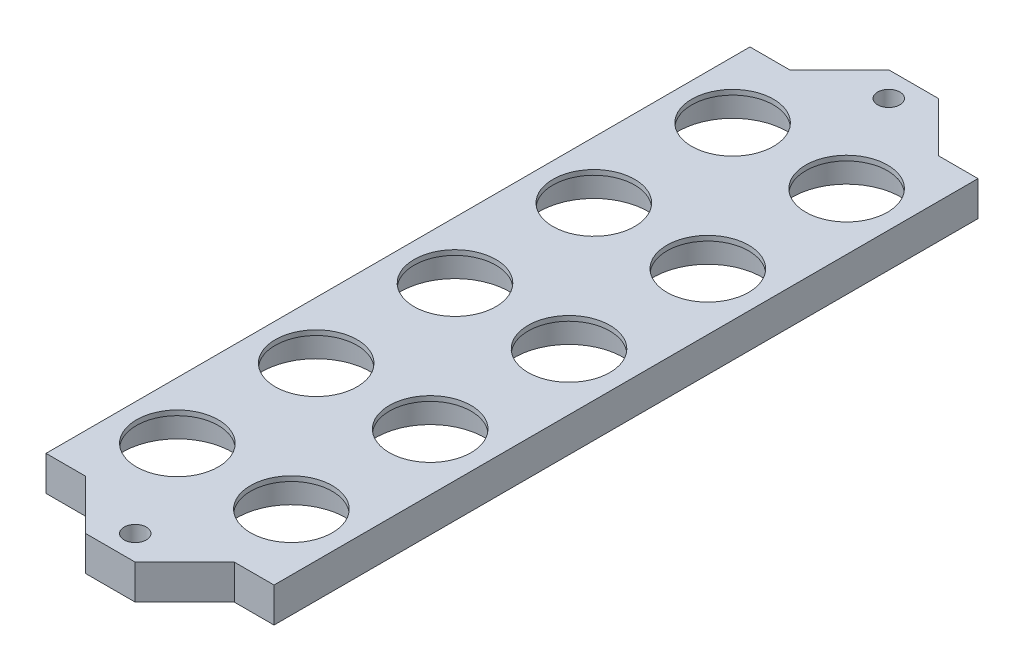
SolidWorks part; units mm, degrees
ref_plane "Front Plane" through (0, 0, 0) normal (0, 0, 1) x (1, 0, 0)
ref_plane "Top Plane" through (0, 0, 0) normal (0, 1, 0) x (1, 0, 0)
ref_plane "Right Plane" through (0, 0, 0) normal (1, 0, 0) x (0, 0, -1)
sketch "Szkic1" plane through (0, 0, 0) normal (0, 1, 0) x (1, 0, 0)
  line L0 (6.5, 25) -> (-3.5, 15)
  line L1 (-11.5, 15) -> (34.5, 15)
  line L2 (-11.5, 15) -> (-11.5, -127)
  line L3 (-11.5, -127) -> (34.5, -127)
  line L4 (34.5, 15) -> (34.5, -127)
  line L5 (6.5, 15) -> (16.5, 15)
  line L6 (6.5, 15) -> (6.5, 25)
  line L7 (6.5, 25) -> (16.5, 25)
  line L8 (16.5, 15) -> (16.5, 25)
  line L9 (16.5, 25) -> (26.5, 15)
  line L12 (-11.5, -56) -> (-33.554, -56) construction
  line L13 (16.5, -137) -> (26.5, -127)
  line L14 (16.5, -127) -> (16.5, -137)
  line L15 (6.5, -127) -> (6.5, -137)
  line L16 (6.5, -137) -> (16.5, -137)
  line L17 (6.5, -137) -> (-3.5, -127)
  line L18 (-11.5, -155) -> (34.5, -155) [skipped]
  line L19 (-11.5, -183) -> (34.5, -183) [skipped]
  circle A0 centre (0, 0) radius 8.25
  circle A1 centre (0, 0) radius 10.6
  circle A2 centre (0, 0) radius 10.1
  circle A3 centre (0, 0) radius 11
  circle A5 centre (23, 0) radius 8.25
  circle A6 centre (23, 0) radius 10.6
  circle A7 centre (23, 0) radius 10.1
  circle A8 centre (23, 0) radius 11
  circle A10 centre (23, -28) radius 8.25
  circle A11 centre (23, -28) radius 10.6
  circle A12 centre (23, -28) radius 10.1
  circle A13 centre (23, -28) radius 11
  circle A15 centre (0, -28) radius 8.25
  circle A16 centre (0, -28) radius 10.6
  circle A17 centre (0, -28) radius 10.1
  circle A18 centre (0, -28) radius 11
  circle A20 centre (0, -56) radius 11
  circle A21 centre (0, -56) radius 10.6
  circle A22 centre (0, -56) radius 10.1
  circle A23 centre (0, -56) radius 8.25
  circle A24 centre (23, -56) radius 8.25
  circle A25 centre (23, -56) radius 10.1
  circle A26 centre (23, -56) radius 10.6
  circle A27 centre (23, -56) radius 11
  circle A28 centre (0, -84) radius 11
  circle A29 centre (0, -84) radius 10.6
  circle A30 centre (0, -84) radius 10.1
  circle A31 centre (0, -84) radius 8.25
  circle A32 centre (23, -84) radius 8.25
  circle A33 centre (23, -84) radius 10.1
  circle A34 centre (23, -84) radius 10.6
  circle A35 centre (23, -84) radius 11
  circle A36 centre (0, -112) radius 11
  circle A37 centre (0, -112) radius 10.6
  circle A38 centre (0, -112) radius 10.1
  circle A39 centre (0, -112) radius 8.25
  circle A40 centre (23, -112) radius 8.25
  circle A41 centre (23, -112) radius 10.1
  circle A42 centre (23, -112) radius 10.6
  circle A43 centre (23, -112) radius 11
  dimension "D1" = 16.5
  dimension "D2" = 20.2
  dimension "D3" = 21.2
  dimension "D4" = 0.4
  dimension "D5" = 23
  dimension "D8" = 11.5
  dimension "D10" = 2
  dimension "D9" = 11.5
  dimension "D11" = 15
  dimension "D12" = 10
  dimension "D13" = 18
  dimension "D14" = 10
  dimension "D15" = 3
  dimension "D16" = 15
  dimension "D17" = 45
  dimension "D18" = 45
  dimension "D6" = 2
  dimension "D7" = 2
extrude "Dodanie-wyciągnięcie1" add sketch "Szkic1" along normal blind 1 contours L4 L1 L2 | L4 L2 | L2 L3 L4 | A18 | A18 A16 | A16 A17 | A17 A15 | A12 A10 | A11 A12 | A13 A11 | A13 | A7 A5 | A6 A7 | A8 A6 | A8 | A3 | A3 A1 | A1 A2 | A2 A0 | L1 L6 L0 | L1 L8 L7 L6 | L9 L8 L1 | A22 A23 | A21 A22 | A20 A21 | A25 A24 | A26 A25 | A27 A26 | A33 A32 | A34 A33 | A35 A34 | A28 A29 | A29 A30 | A30 A31 | A41 A40 | A42 A41 | A43 A42 | A38 A39 | A37 A38 | A36 A37 | L15 L16 L14 L3 | L17 L15 L3 | L3 L14 L13 region at (3.1667, 0, -18.3333) region at (11.5, 0, -20) region at (11.5, 0, 56) region at (19.8333, 0, -18.3333) region at (3.1667, 0, 130.3333) region at (11.5, 0, 132) region at (19.8333, 0, 130.3333) region at (-10.3002, 0, 0) region at (-9.8143, 0, 0) region at (-10.6889, 0, 0) region at (12.6998, 0, 0) region at (13.1857, 0, 0) region at (12.3111, 0, 0) region at (12.6998, 0, 28) region at (13.1857, 0, 28) region at (12.3111, 0, 28) region at (-10.3002, 0, 28) region at (-9.8143, 0, 28) region at (-10.6889, 0, 28) region at (-10.6889, 0, 56) region at (-10.3002, 0, 56) region at (-9.8143, 0, 56) region at (13.1857, 0, 56) region at (12.6998, 0, 56) region at (12.3111, 0, 56) region at (-10.6889, 0, 84) region at (-10.3002, 0, 84) region at (-9.8143, 0, 84) region at (13.1857, 0, 84) region at (12.6998, 0, 84) region at (12.3111, 0, 84) region at (-10.6889, 0, 112) region at (-10.3002, 0, 112) region at (-9.8143, 0, 112) region at (13.1857, 0, 112) region at (12.6998, 0, 112) region at (12.3111, 0, 112)
extrude "Dodanie-wyciągnięcie2" add sketch "Szkic1<3>" against normal blind 6 from surface contours A3 | A8 | L4 L1 L2 | L4 L2 | A18 | A13 | L2 L3 L4 | L1 L6 L0 | L1 L8 L7 L6 | L9 L8 L1 | L17 L15 L3 | L15 L16 L14 L3 | L3 L14 L13 region at (3.1667, 0, -18.3333) region at (11.5, 0, -20) region at (11.5, 0, 56) region at (19.8333, 0, -18.3333) region at (3.1667, 0, 130.3333) region at (11.5, 0, 132) region at (19.8333, 0, 130.3333) starting at face at (11.5, 0, 56)
sketch "Szkic1<3>" plane through (0, 0, 0) normal (0, 1, 0) x (1, 0, 0) same geometry as "Szkic1"
sketch "Szkic2" plane through (0, 1, 0) normal (0, 1, 0) x (1, 0, 0)
  line L0 (-11.5, 15) -> (34.5, 15)
  line L1 (11.5, 15) -> (11.5, 25)
  line L2 (6.5, 25) -> (16.5, 25) construction
  line L3 (-11.5, -56) -> (34.5, -56) construction
  line L4 (-11.5, 15) -> (-11.5, -127) construction
  line L5 (34.5, 15) -> (34.5, -127) construction
  circle A0 centre (11.5, 20) radius 2.25
  circle A1 centre (11.5, -132) radius 2.25
  dimension "D1" = 4.5
extrude "Wytnij-wyciągnięcie1" cut sketch "Szkic2" against normal blind 20 contours L1 A0 | L1 A0 | A1 region at (10.5451, 1, -20) region at (12.4549, 1, -20) region at (11.5, 1, 132)
sketch "Szkic6" plane through (0, -6, 0) normal (0, -1, 0) x (1, 0, 0)
  line L0 (34.5, 56) -> (-28.922, 56)
  line L1 (34.5, 127) -> (34.5, -15) construction
  circle A0 centre (11.5, 132) radius 4.05
  circle A1 centre (11.5, -20) radius 4.05
  dimension "D1" = 8.1
extrude "Wytnij-wyciągnięcie2" cut sketch "Szkic6" against normal blind 1 contours A0 | A1
